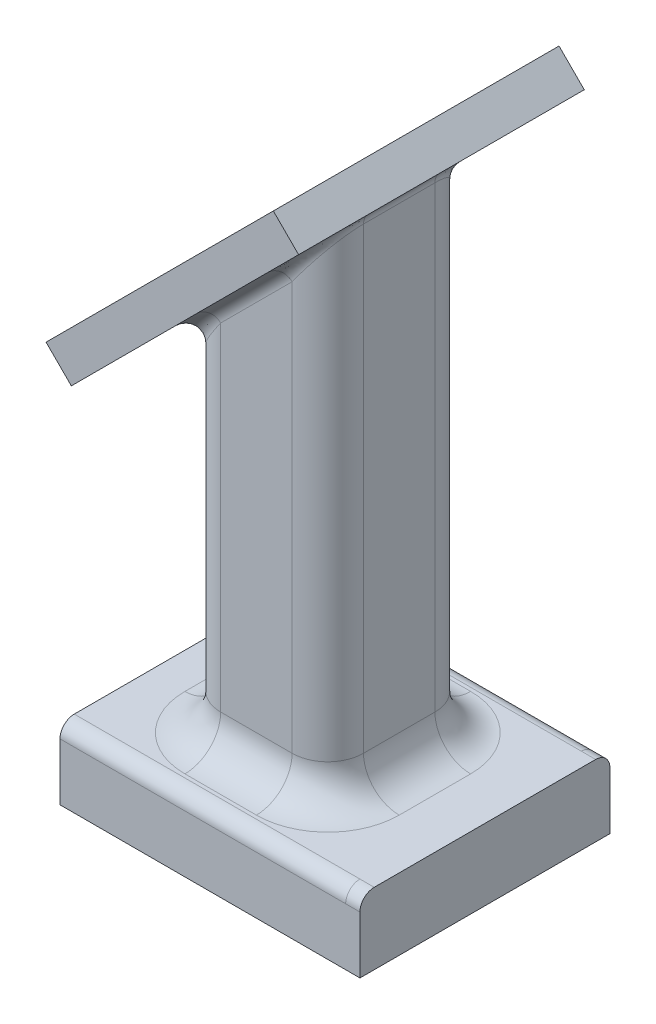
SolidWorks part; units mm, degrees
ref_plane "Front Plane" through (0, 0, 0) normal (0, 0, 1) x (1, 0, 0)
ref_plane "Top Plane" through (0, 0, 0) normal (0, 1, 0) x (1, 0, 0)
ref_plane "Right Plane" through (0, 0, 0) normal (1, 0, 0) x (0, 0, -1)
sketch "Sketch1" plane through (0, 0, 0) normal (1, 0, 0) x (0, 0, -1)
  line L0 (-11.4, 0) -> (-17.5, 0)
  line L1 (-17.5, 0) -> (-17.5, 10)
  line L2 (-17.5, 10) -> (17.5, 10)
  line L3 (17.5, 10) -> (17.5, 0)
  line L4 (17.5, 0) -> (11.4, 0)
  line L5 (11.4, 0) -> (11.4, 2.35)
  line L6 (11.4, 2.35) -> (13.9, 2.35)
  line L7 (13.9, 2.35) -> (13.9, 7.6)
  line L8 (13.9, 7.6) -> (3.6, 7.6)
  line L9 (3.6, 7.6) -> (3.6, 2.35)
  line L10 (3.6, 2.35) -> (6.1, 2.35)
  line L11 (6.1, 2.35) -> (6.1, 0)
  line L12 (6.1, 0) -> (-6.1, 0)
  line L13 (-6.1, 0) -> (-6.1, 2.35)
  line L14 (-6.1, 2.35) -> (-3.6, 2.35)
  line L15 (-3.6, 2.35) -> (-3.6, 7.6)
  line L16 (-3.6, 7.6) -> (-13.9, 7.6)
  line L17 (-13.9, 7.6) -> (-13.9, 2.35)
  line L18 (-13.9, 2.35) -> (-11.4, 2.35)
  line L19 (-11.4, 2.35) -> (-11.4, 0)
  point P10 (0, 0)
  point P22 (0, 10)
  dimension "D1" = 2.35
  dimension "D2" = 12.2
  dimension "D3" = 35
  dimension "D4" = 5.3
  dimension "D5" = 10
  dimension "D6" = 5.3
  dimension "D7" = 5.25
  dimension "D8" = 5.25
  dimension "D9" = 2.5
extrude "Boss-Extrude1" add sketch "Sketch1" along normal blind 40
sketch "Sketch2" plane through (40, 0, 0) normal (1, 0, 0) x (0, 0, -1)
  line L0 (17.5, 10) -> (-17.5, 10) construction
  line L1 (-10, 10) -> (10, 10)
  line L2 (-10, 10) -> (-10, 80)
  line L3 (-10, 80) -> (10, 80)
  line L4 (10, 10) -> (10, 80)
  point P6 (0, 10)
  dimension "D1" = 70
  dimension "D2" = 20
extrude "Boss-Extrude2" add sketch "Sketch2" against normal blind 20 from offset 10 offset against normal yes
fillet "Fillet2" radius 2 2 edges at (20, 10, -17.5) (20, 10, 17.5)
sketch "Sketch3" plane through (0, 0, -10) normal (0, 0, -1) x (-1, 0, 0)
  line L0 (-30, 80) -> (-10, 80)
  line L1 (-10, 80) -> (-10, 60)
  line L2 (-10, 10) -> (-10, 80) construction
  line L3 (-10, 60) -> (-30, 80)
  dimension "D1" = 45
extrude "Cut-Extrude1" cut sketch "Sketch3" against normal up to surface (20 mm away) up to face at (20, 45, 10)
sketch "Sketch4" plane through (-25, 25, 0) normal (-0.7071, 0.7071, 0) x (0, 0, 1)
  line L1 (-20, 86.1396) -> (20, 86.1396)
  line L2 (-20, 86.1396) -> (-20, 41.1396)
  line L3 (-20, 41.1396) -> (20, 41.1396)
  line L4 (20, 86.1396) -> (20, 41.1396)
  line L6 (-10, 77.7817) -> (10, 77.7817) construction
  line L7 (-10, 77.7817) -> (-10, 49.4975) construction
  point P6 (0, 77.7817)
  point P7 (0, 86.1396)
  point P10 (-10, 63.6396)
  point P11 (-20, 63.6396)
  dimension "D1" = 45
  dimension "D2" = 40
extrude "Boss-Extrude3" add sketch "Sketch4" along normal blind 5
sketch "Sketch5" plane through (-28.5355, 28.5355, 0) normal (-0.7071, 0.7071, 0) x (0, 0, 1)
  line L0 (20, 86.1396) -> (-20, 86.1396) construction
  line L1 (-20, 86.1396) -> (-20, 41.1396) construction
  line L2 (20, 41.1396) -> (20, 86.1396) construction
  line L3 (-20, 41.1396) -> (20, 41.1396) construction
  circle A0 centre (-15, 81.1396) radius 1.55
  circle A1 centre (15, 81.1396) radius 1.55
  circle A2 centre (15, 46.1396) radius 1.55
  circle A3 centre (-15, 46.1396) radius 1.55
  dimension "D1" = 3.1
  dimension "D4" = 5
  dimension "D5" = 5
  dimension "D2" = 5
  dimension "D3" = 5
extrude "Cut-Extrude2" cut sketch "Sketch5" against normal up to surface (5 mm away) up to face at (20, 70, 0)
fillet "Fillet4" radius 5 8 edges at (10, 10, 0) (20, 10, 10) (20, 10, -10) (30, 10, 0) (10, 35, 10) (10, 35, -10) (30, 45, -10) (30, 45, 10)
fillet "Fillet5" radius 2 8 edges at (11.4645, 61.4645, 8.5355) (11.4645, 61.4645, -8.5355) (20, 70, -10) (20, 70, 10) (28.5355, 78.5355, 8.5355) (28.5355, 78.5355, -8.5355) (30, 80, 0) (10, 60, 0)
sketch "Sketch6" plane through (40, 0, 0) normal (1, 0, 0) x (0, 0, -1)
  line L1 (17.5, 10) -> (-17.5, 10)
  line L2 (17.5, 10) -> (17.5, 0)
  line L3 (17.5, 0) -> (-17.5, 0)
  line L4 (-17.5, 10) -> (-17.5, 0)
  dimension "D1" = 10
extrude "Boss-Extrude4" add sketch "Sketch6" along normal blind 2
fillet "Fillet6" radius 2 2 edges at (41, 10, -17.5) (41, 10, 17.5)
